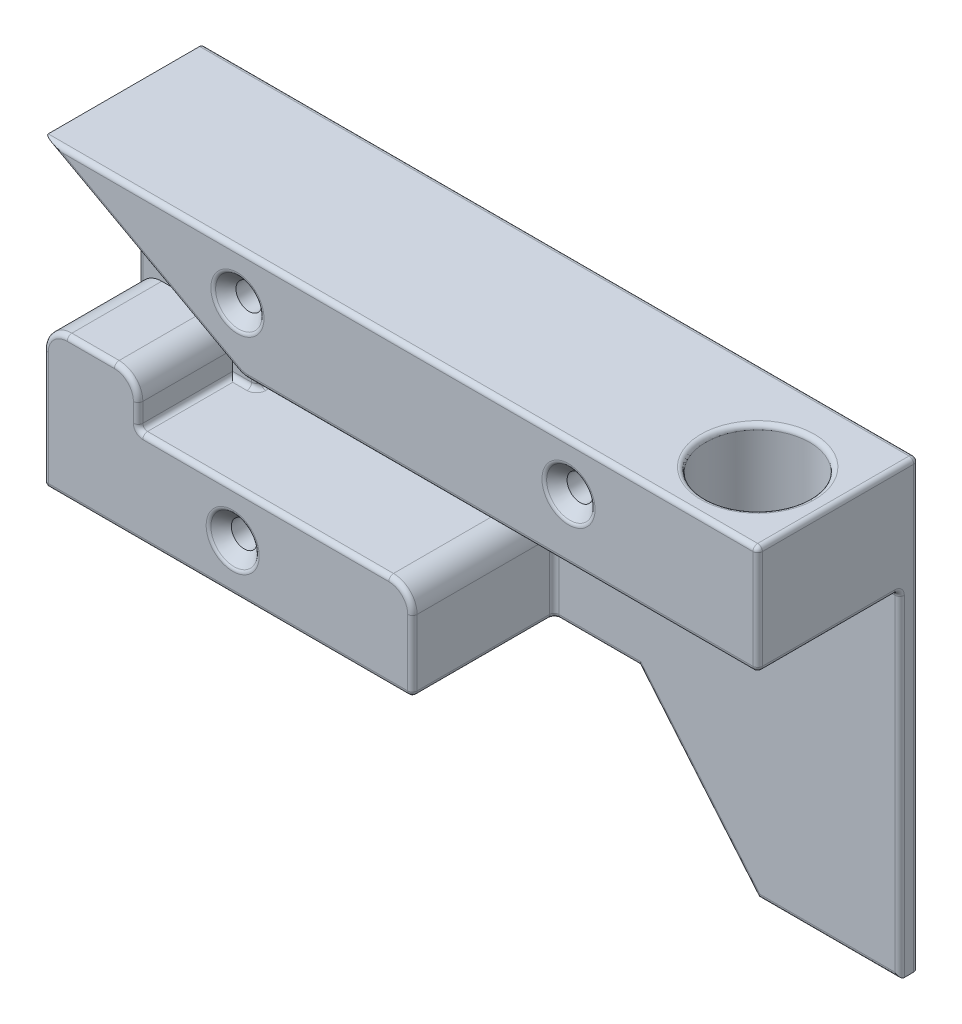
SolidWorks part; units mm, degrees
ref_plane "Front Plane" through (0, 0, 0) normal (0, 0, 1) x (1, 0, 0)
ref_plane "Top Plane" through (0, 0, 0) normal (0, 1, 0) x (1, 0, 0)
ref_plane "Right Plane" through (0, 0, 0) normal (1, 0, 0) x (0, 0, -1)
sketch "Sketch1" plane through (0, 0, 0) normal (0, 0, 1) x (1, 0, 0)
  line L0 (95.827, 0) -> (121, -30)
  line L1 (0, 0) -> (95.827, 0)
  line L2 (0, 0) -> (0, 64)
  line L3 (0, 64) -> (151, 64)
  line L4 (151, -30) -> (151, 64)
  line L5 (121, -30) -> (151, -30)
  dimension "D1" = 64
  dimension "D2" = 151
  dimension "D3" = 30
  dimension "D4" = 30
  dimension "D5" = 130
extrude "Boss-Extrude1" add sketch "Sketch1" along normal blind 4
sketch "Sketch2" plane through (0, 0, 4) normal (0, 0, 1) x (1, 0, 0)
  line L0 (0, 64) -> (151, 64)
  line L1 (151, 64) -> (151, 41)
  line L2 (151, -30) -> (151, 64) construction
  line L3 (151, 41) -> (42, 41)
  line L4 (42, 41) -> (0, 64)
  line L6 (20, 20) -> (20, 30)
  line L7 (20, 30) -> (0, 30)
  line L8 (0, 64) -> (0, 0) construction
  line L9 (0, 30) -> (0, 0)
  line L12 (20, 20) -> (78, 20)
  line L13 (78, 20) -> (78, 0)
  line L14 (0, 0) -> (95.827, 0) construction
  line L15 (78, 0) -> (0, 0)
  dimension "D1" = 23
  dimension "D2" = 42
  dimension "D3" = 20
  dimension "D4" = 10
  dimension "D5" = 20
  dimension "D6" = 78
extrude "Boss-Extrude2" add sketch "Sketch2" along normal blind 30
sketch "Sketch3" plane through (0, 0, 4) normal (0, 0, 1) x (1, 0, 0)
  line L0 (25, 20) -> (25, 50.3095)
  line L1 (78, 20) -> (20, 20) construction
  line L2 (0, 64) -> (42, 41) construction
  line L3 (25, 50.3095) -> (0, 64)
  line L4 (0, 64) -> (0, 30)
  line L5 (0, 30) -> (20, 30)
  line L6 (20, 30) -> (20, 20)
  line L7 (20, 20) -> (25, 20)
  dimension "D1" = 25
extrude "Boss-Extrude3" add sketch "Sketch3" along normal blind 10
sketch "Sketch4" plane through (0, 0, 4) normal (0, 0, 1) x (1, 0, 0)
  line L0 (25, 50.3095) -> (42, 41)
  line L1 (42, 41) -> (69, 41)
  line L2 (42, 41) -> (151, 41) construction
  line L3 (69, 41) -> (69, 20)
  line L4 (78, 20) -> (25, 20) construction
  line L5 (69, 20) -> (25, 20)
  line L6 (25, 20) -> (25, 50.3095)
  dimension "D1" = 44
extrude "Boss-Extrude4" add sketch "Sketch4" along normal blind 5
fillet "Fillet1" radius 5 4 edges at (20, 30, 24) (78, 20, 19) (42, 41, 21.5) (0, 30, 24)
sketch "Sketch5" plane through (0, 64, 0) normal (0, 1, 0) x (1, 0, 0)
  line L0 (151, -34) -> (151, -4) construction
  line L2 (0, -14) -> (0, 0) construction
  circle A0 centre (136, -19) radius 11
  point P5 (151, -19)
  dimension "D1" = 22
  dimension "D2" = 136
extrude "Cut-Extrude1" cut sketch "Sketch5" against normal up to next
hole_wizard "CSK for M5 Countersunk Flat Head Screw1" positions "Sketch8" profile "Sketch9" countersink size "M5" standard "ISO"
sketch "Sketch8" plane through (0, 0, 34) normal (0, 0, 1) x (1, 0, 0)
  line L2 (151, 41) -> (151, 64) construction
  line L3 (151, 64) -> (0, 64) construction
  line L4 (0, 0) -> (78, 0) construction
  line L6 (0, 25) -> (0, 0) construction
  point P0 (41, 54)
  point P2 (111, 54)
  point P4 (40, 10)
  dimension "D1" = 70
  dimension "D2" = 40
  dimension "D3" = 10
  dimension "D4" = 10
  dimension "D5" = 40
sketch "Sketch9" plane through (41, 54, 34) normal (1, 0, 0) x (0, -1, 0)
  line L0 (0, 0) -> (0, 25.6524)
  line L1 (0, 25.6524) -> (2.75, 24)
  line L2 (2.75, 24) -> (2.75, 2.45)
  line L3 (2.75, 2.45) -> (5.2, 0)
  line L5 (5.2, 0) -> (0, 0)
  line L6 (-2.75, 2.45) -> (-5.2, 0) construction
  line L10 (0, 25.6524) -> (-2.75, 24) construction
  line L11 (0, -6.35) -> (0, 107.95) construction
  dimension "Hole Dia." = 5.5
  dimension "Hole Depth" = 24
  dimension "Near C'Sink Dia." = 10.4
  dimension "Near C'Sink Angle" = 90
  dimension "Drill Angle" = 118
fillet "Fillet3" radius 1 52 edges at (151, 41, 19) (20, 20, 24) (22.5, 20, 14) (25, 20, 11.5) (32.9389, 45.962, 9) (42.0399, 41.1561, 9) (56.1397, 41, 9) (47, 20, 9) (25, 35.1548, 9) (110, 41, 4) (151, 5.5, 4) (136, -30, 4) (108.4135, -15, 4) (86.9135, 0, 4) (76.5355, 18.5355, 4) (71, 20, 4) (69, 20, 6.5) (69, 30.5, 9) (69, 41, 6.5) (69, 30.5, 4) (75.5, 64, 34) (151, 52.5, 34) (97.1397, 41, 34) (42.0399, 41.1561, 34) (20.4389, 52.8073, 34) (116.2, 54, 34) (46.2, 54, 34) (39, 0, 34) (0, 12.5, 34) (1.4645, 28.5355, 34) (10, 30, 34) (18.5355, 28.5355, 34) (20, 22.5, 34) (46.5, 20, 34) (76.5355, 18.5355, 34) (45.2, 10, 34) (78, 0, 19) (78, 7.5, 34) (78, 7.5, 4) (47.9135, 0, 0) (108.4135, -15, 0) (136, -30, 0) (151, 17, 0) (75.5, 64, 0) (0, 32, 0) (0, 0, 17) (125, 41, 19) (136, 64, 30) (151, 64, 17) (0, 44.5, 14) (25, 35.1548, 14) (42.75, 10, 10)
